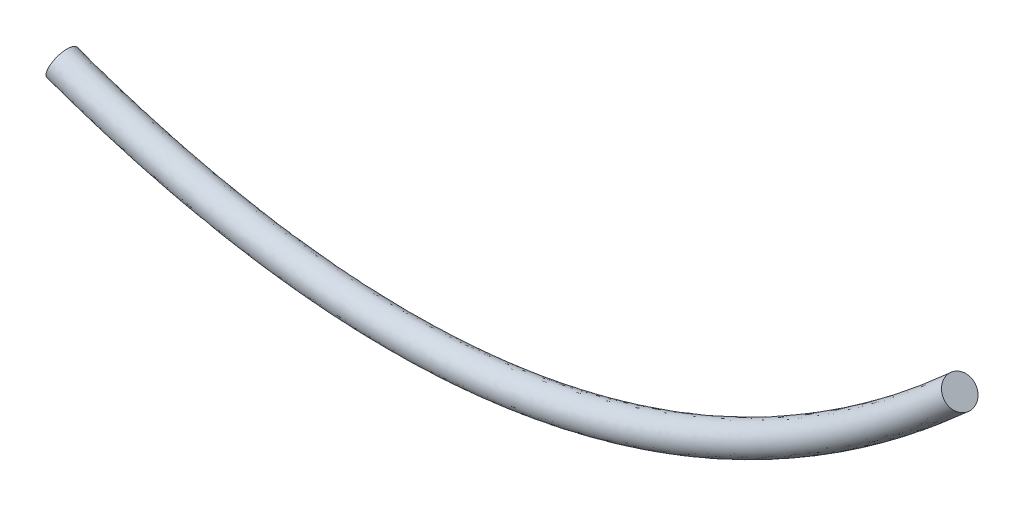
SolidWorks part; units mm, degrees
ref_plane "Front Plane" through (0, 0, 0) normal (0, 0, 1) x (1, 0, 0)
ref_plane "Top Plane" through (0, 0, 0) normal (0, 1, 0) x (1, 0, 0)
ref_plane "Right Plane" through (0, 0, 0) normal (1, 0, 0) x (0, 0, -1)
sketch "Sketch4" plane through (0, 0, 0) normal (0, 0, 1) x (1, 0, 0)
  spline S2 degree 2 poles (-63.0935, -14.1452) (39.6891, -59.5534) (113.5618, 18.4575) knots 0 0 0 1 1 1 construction
  spline S3 degree 2 poles (-48.1095, -20.1647) (37.3785, -51.0105) (102.0119, 7.1737) knots 0.073655 0.073655 0.073655 0.922986 0.922986 0.922986
ref_plane "Plane3" through (-48.1095, -20.1647, 0) normal (0.9406, -0.3394, 0) x (0, 0, -1)
sketch "Sketch7" plane through (-48.1095, -20.1647, 0) normal (0.9406, -0.3394, 0) x (0, 0, -1)
  circle A0 centre (0, 0) radius 2.54
  point P4 (0, 0)
  dimension "D1" = 5.08
sweep "Sweep1" add profiles "Sketch7" path "Sketch4"
